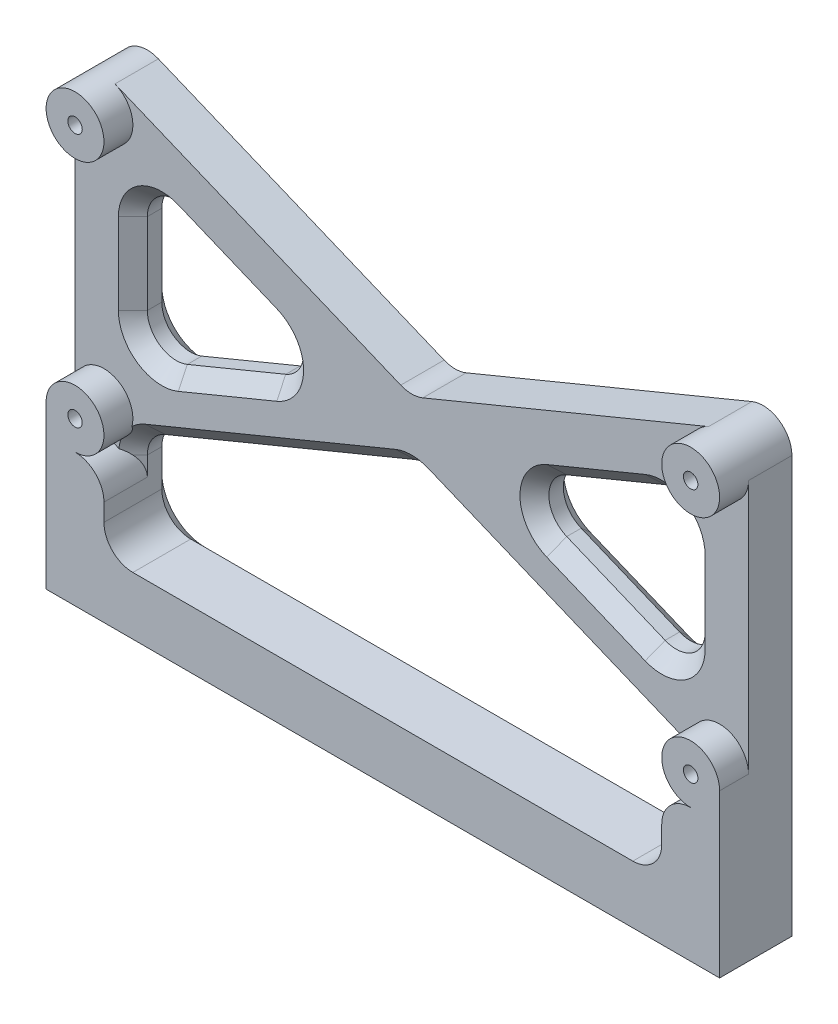
SolidWorks part; units mm, degrees
ref_plane "Ebene vorne" through (0, 0, 0) normal (0, 0, 1) x (1, 0, 0)
ref_plane "Ebene oben" through (0, 0, 0) normal (0, 1, 0) x (1, 0, 0)
ref_plane "Ebene rechts" through (0, 0, 0) normal (1, 0, 0) x (0, 0, -1)
sketch "Sketch1" plane through (0, 0, 0) normal (0, 0, 1) x (1, 0, 0)
  line L0 (-23.285, 8.79) -> (-23.285, -8.79)
  line L1 (-21.285, -8.79) -> (21.285, -8.79) construction
  line L2 (-21.285, -8.79) -> (-21.285, 8.79) construction
  line L3 (-21.285, 8.79) -> (21.285, 8.79) construction
  line L4 (21.285, -8.79) -> (21.285, 8.79) construction
  line L5 (-21.285, -8.79) -> (21.285, 8.79) construction
  line L6 (-21.285, 8.79) -> (21.285, -8.79) construction
  line L7 (19.285, 2.8105) -> (19.285, -2.8105)
  line L8 (23.285, 8.79) -> (23.285, -8.79)
  line L9 (16.5216, -4.659) -> (9.716, -1.8486)
  line L10 (-9.716, -1.8486) -> (-16.5216, -4.659)
  line L11 (-0.7634, 2.4791) -> (-20.5216, 10.6386)
  line L12 (-18.0484, -9.6172) -> (-0.7634, -2.4791)
  line L13 (20.5216, 10.6386) -> (0.7634, 2.4791)
  line L14 (0, 0) -> (0, -20) construction
  line L15 (23.285, -20) -> (-23.285, -20)
  line L16 (-23.285, -8.79) -> (-23.285, -20)
  line L17 (23.285, -8.79) -> (23.285, -20)
  line L18 (19.285, -11.4658) -> (19.285, -14)
  line L19 (-19.285, -11.4658) -> (-19.285, -14)
  line L20 (-17.285, -16) -> (17.285, -16)
  line L21 (-19.285, 2.8105) -> (-19.285, -2.8105)
  line L22 (-16.5216, 4.659) -> (-9.716, 1.8486)
  line L23 (0.7634, -2.4791) -> (18.0484, -9.6172)
  line L24 (9.716, 1.8486) -> (16.5216, 4.659)
  circle A0 centre (-21.285, 8.79) radius 0.5
  circle A1 centre (21.285, 8.79) radius 0.5
  circle A2 centre (21.285, -8.79) radius 0.5
  circle A3 centre (-21.285, -8.79) radius 0.5
  arc A8 (-20.5216, 10.6386) -> (-23.285, 8.79) centre (-21.285, 8.79) ccw
  arc A9 (23.285, 8.79) -> (20.5216, 10.6386) centre (21.285, 8.79) ccw
  arc A10 (-17.285, -16) -> (-19.285, -14) centre (-17.285, -14) cw
  arc A11 (17.285, -16) -> (19.285, -14) centre (17.285, -14) ccw
  arc A12 (18.0484, -9.6172) -> (19.285, -11.4658) centre (17.285, -11.4658) cw
  arc A13 (0.7634, 2.4791) -> (-0.7634, 2.4791) centre (0, 4.3277) cw
  arc A14 (9.716, -1.8486) -> (9.716, 1.8486) centre (10.4794, 0) cw
  arc A15 (19.285, 2.8105) -> (16.5216, 4.659) centre (17.285, 2.8105) ccw
  arc A16 (19.285, -2.8105) -> (16.5216, -4.659) centre (17.285, -2.8105) cw
  arc A17 (-19.285, -2.8105) -> (-16.5216, -4.659) centre (-17.285, -2.8105) ccw
  arc A18 (-19.285, 2.8105) -> (-16.5216, 4.659) centre (-17.285, 2.8105) cw
  arc A19 (-9.716, -1.8486) -> (-9.716, 1.8486) centre (-10.4794, 0) ccw
  arc A20 (-18.0484, -9.6172) -> (-19.285, -11.4658) centre (-17.285, -11.4658) ccw
  arc A21 (0.7634, -2.4791) -> (-0.7634, -2.4791) centre (0, -4.3277) ccw
  point P0 (0, 0)
  point P35 (0, -20)
  point P41 (0, 2.1638)
  point P58 (0, -2.1638)
  dimension "D3" = 1
  dimension "D4" = 2
  dimension "D1" = 42.57
  dimension "D2" = 17.58
  dimension "D5" = 20
  dimension "D6" = 4
extrude "Boss-Extrude1" add sketch "Sketch1" along normal blind 5
sketch "Sketch2" plane through (0, -20, 0) normal (0, -1, 0) x (1, 0, 0)
  line L0 (-23.285, 2.5) -> (23.285, 2.5) construction
  line L1 (-23.285, 5) -> (-23.285, 0) construction
  line L2 (23.285, 5) -> (23.285, 0) construction
  circle A0 centre (-21.285, 2.5) radius 1.35
  circle A1 centre (21.285, 2.5) radius 1.35
  dimension "D3" = 2.7
  dimension "D4" = 2.7
  dimension "D1" = 2
  dimension "D2" = 2
extrude "Cut-Extrude1" cut sketch "Sketch2" against normal blind 8
sketch "Sketch3" plane through (0, 0, 5) normal (0, 0, 1) x (1, 0, 0)
  line L0 (-21.285, -10.79) -> (21.285, -10.79)
  line L1 (23.285, -8.79) -> (23.285, 8.79)
  line L2 (21.285, 10.79) -> (-21.285, 10.79)
  line L3 (-23.285, 8.79) -> (-23.285, -8.79)
  arc A0 (-23.285, 8.79) -> (-21.285, 10.79) centre (-21.285, 8.79) ccw
  arc A1 (21.285, 10.79) -> (23.285, 8.79) centre (21.285, 8.79) ccw
  arc A2 (23.285, -8.79) -> (21.285, -10.79) centre (21.285, -8.79) ccw
  arc A3 (-21.285, -10.79) -> (-23.285, -8.79) centre (-21.285, -8.79) ccw
extrude "Cut-Extrude2" cut sketch "Sketch3" against normal blind 2
fillet "Fillet1" radius 2 2 edges at (19.1674, -10.79, 4) (-19.1674, -10.79, 4)
chamfer "Chamfer1" distance 1 angle 45 41 edges at (18.397, 4.4728, 3) (13.1188, 3.2538, 3) (19.285, 0, 3) (8.4794, 0, 3) (18.397, -4.4728, 3) (13.1188, -3.2538, 3) (-19.285, 0, 3) (-18.397, -4.4728, 3) (-18.397, 4.4728, 3) (-13.1188, -3.2538, 3) (-13.1188, 3.2538, 3) (-8.4794, 0, 3) (-19.285, -12.1279, 3) (-18.9473, -10.3538, 3) (19.285, -12.1279, 3) (-9.4059, -6.0482, 3) (18.9473, -10.3538, 3) (0, -2.3277, 3) (9.4059, -6.0482, 3) (0, -2.3277, 0) (-9.4059, -6.0482, 0) (9.4059, -6.0482, 0) (-18.9473, -10.3538, 0) (18.9473, -10.3538, 0) (-19.285, -12.7329, 0) (19.285, -12.7329, 0) (-18.6992, -15.4142, 0) (18.6992, -15.4142, 0) (0, -16, 0) (-18.397, 4.4728, 0) (-19.285, 0, 0) (-13.1188, 3.2538, 0) (-18.397, -4.4728, 0) (-8.4794, 0, 0) (-13.1188, -3.2538, 0) (8.4794, 0, 0) (13.1188, -3.2538, 0) (13.1188, 3.2538, 0) (18.397, -4.4728, 0) (18.397, 4.4728, 0) (19.285, 0, 0)
